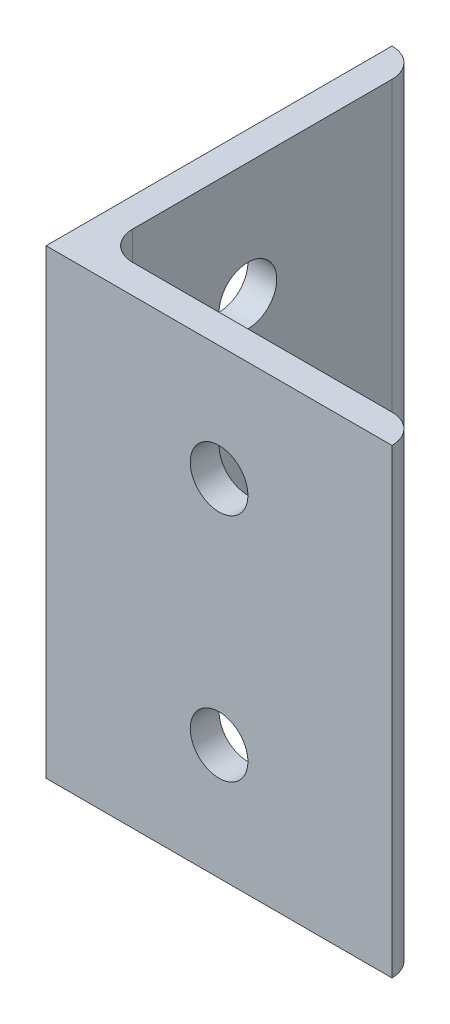
SolidWorks part; units mm, degrees
ref_plane "Front Plane" through (0, 0, 0) normal (0, 0, 1) x (1, 0, 0)
ref_plane "Top Plane" through (0, 0, 0) normal (0, 1, 0) x (1, 0, 0)
ref_plane "Right Plane" through (0, 0, 0) normal (1, 0, 0) x (0, 0, -1)
sketch "Sketch1" plane through (0, 0, 0) normal (0, 1, 0) x (1, 0, 0)
  line L0 (0, 38.1) -> (0, 0)
  line L1 (0, 0) -> (38.1, 0)
  dimension "D1" = 38.1
  dimension "D2" = 38.1
extrude "Extrude-Thin1" add sketch "Sketch1" along normal mid plane 50.8 thin thin type one direction reverse wall 3.175
fillet "Fillet1" radius 3.175 3 edges at (3.175, 0, -3.175) (38.1, 0, -3.175) (3.175, 0, -38.1)
sketch "Sketch2" plane through (0, 0, -3.175) normal (0, 0, -1) x (-1, 0, 0)
  line L0 (-38.1, 12.7) -> (0, 12.7) construction
  line L1 (-38.1, 25.4) -> (-38.1, -25.4) construction
  line L2 (0, 25.4) -> (0, -25.4) construction
  line L3 (0, 25.4) -> (-38.1, 25.4) construction
  circle A0 centre (-19.05, 12.7) radius 3.175
  circle A1 centre (-19.05, -12.7) radius 3.175
  dimension "D2" = 12.7
  dimension "D3" = 6.35
  dimension "D1" = 38.1
  dimension "D4" = 2
extrude "Cut-Extrude1" cut sketch "Sketch2" against normal through all
sketch "Sketch3" plane through (0, 0, 0) normal (-1, 0, 0) x (0, 0, 1)
  line L0 (-38.1, 25.4) -> (0, 25.4) construction
  circle A0 centre (-19.05, 12.7) radius 3.175
  circle A1 centre (-19.05, -12.7) radius 3.175
  point P2 (-19.05, 25.4)
  dimension "D1" = 6.35
  dimension "D2" = 12.7
  dimension "D3" = 2
extrude "Cut-Extrude2" cut sketch "Sketch3" against normal through all
